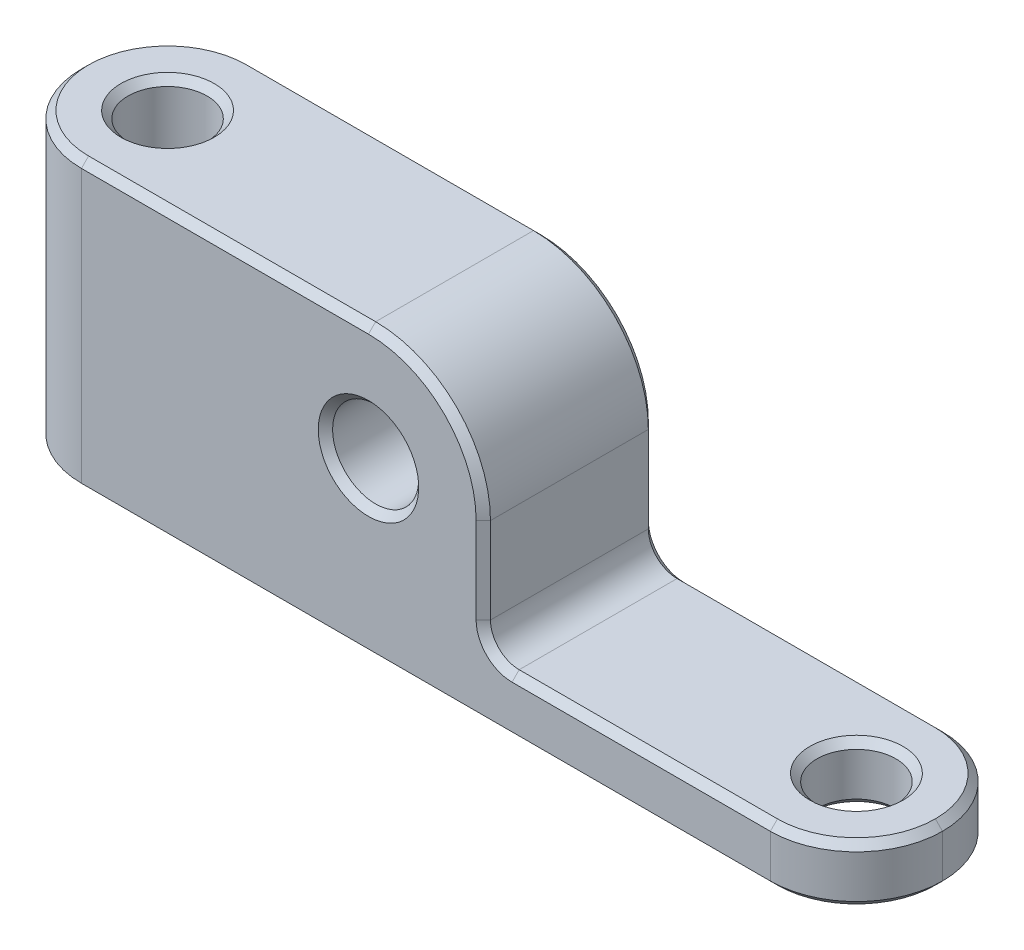
SolidWorks part; units mm, degrees
ref_plane "Front Plane" through (0, 0, 0) normal (0, 0, 1) x (1, 0, 0)
ref_plane "Top Plane" through (0, 0, 0) normal (0, 1, 0) x (1, 0, 0)
ref_plane "Right Plane" through (0, 0, 0) normal (1, 0, 0) x (0, 0, -1)
sketch "Sketch1" plane through (0, 0, 0) normal (0, 0, 1) x (1, 0, 0)
  line L0 (0, 0) -> (0, 15.875)
  line L1 (0, 15.875) -> (20.6375, 15.875)
  line L2 (26.9875, 9.525) -> (26.9875, 4.7625)
  line L3 (28.575, 3.175) -> (47.625, 3.175)
  line L4 (47.625, 3.175) -> (47.625, 0)
  line L5 (47.625, 0) -> (0, 0)
  circle A0 centre (20.6375, 9.525) radius 2.3813
  arc A1 (20.6375, 15.875) -> (26.9875, 9.525) centre (20.6375, 9.525) cw
  arc A2 (26.9875, 4.7625) -> (28.575, 3.175) centre (28.575, 4.7625) ccw
  dimension "D6" = 4.7625
  dimension "D8" = 6.35
  dimension "D9" = 1.5875
  dimension "D1" = 6.35
  dimension "D2" = 47.625
  dimension "D3" = 20.6375
  dimension "D4" = 6.35
  dimension "D5" = 9.525
  dimension "D7" = 3.175
extrude "Boss-Extrude1" add sketch "Sketch1" along normal blind 9.525
sketch "Sketch2" plane through (0, 15.875, 0) normal (0, 1, 0) x (1, 0, 0)
  line L0 (0, -9.525) -> (0, 0) construction
  line L1 (20.6375, -9.525) -> (0, -9.525) construction
  circle A0 centre (4.7625, -4.7625) radius 2.1828
  circle A1 centre (42.8625, -4.7625) radius 2.1828
  dimension "D3" = 4.3656
  dimension "D5" = 4.3656
  dimension "D1" = 4.7625
  dimension "D2" = 4.7625
  dimension "D4" = 38.1
extrude "Cut-Extrude1" cut sketch "Sketch2" against normal through all both and the other way through all
fillet "Fillet1" radius 4.7625 4 edges at (47.625, 1.5875, 9.525) (47.625, 1.5875, 0) (0, 7.9375, 0) (0, 7.9375, 9.525)
chamfer "Chamfer1" distance 0.3969 angle 45 26 edges at (6.9453, 15.875, 4.7625) (23.0188, 9.525, 0) (23.0188, 9.525, 9.525) (23.8125, 0, 0) (1.3949, 0, 1.3949) (1.3949, 0, 8.1301) (23.8125, 0, 9.525) (46.2301, 0, 8.1301) (46.2301, 0, 1.3949) (4.7625, 0, 6.9453) (1.3949, 15.875, 1.3949) (1.3949, 15.875, 8.1301) (12.7, 15.875, 0) (12.7, 15.875, 9.525) (25.1276, 14.0151, 0) (25.1276, 14.0151, 9.525) (26.9875, 7.1437, 0) (26.9875, 7.1437, 9.525) (27.4525, 3.64, 0) (27.4525, 3.64, 9.525) (35.7188, 3.175, 0) (46.2301, 3.175, 1.3949) (46.2301, 3.175, 8.1301) (35.7188, 3.175, 9.525) (42.8625, 0, 6.9453) (45.0453, 3.175, 4.7625)
